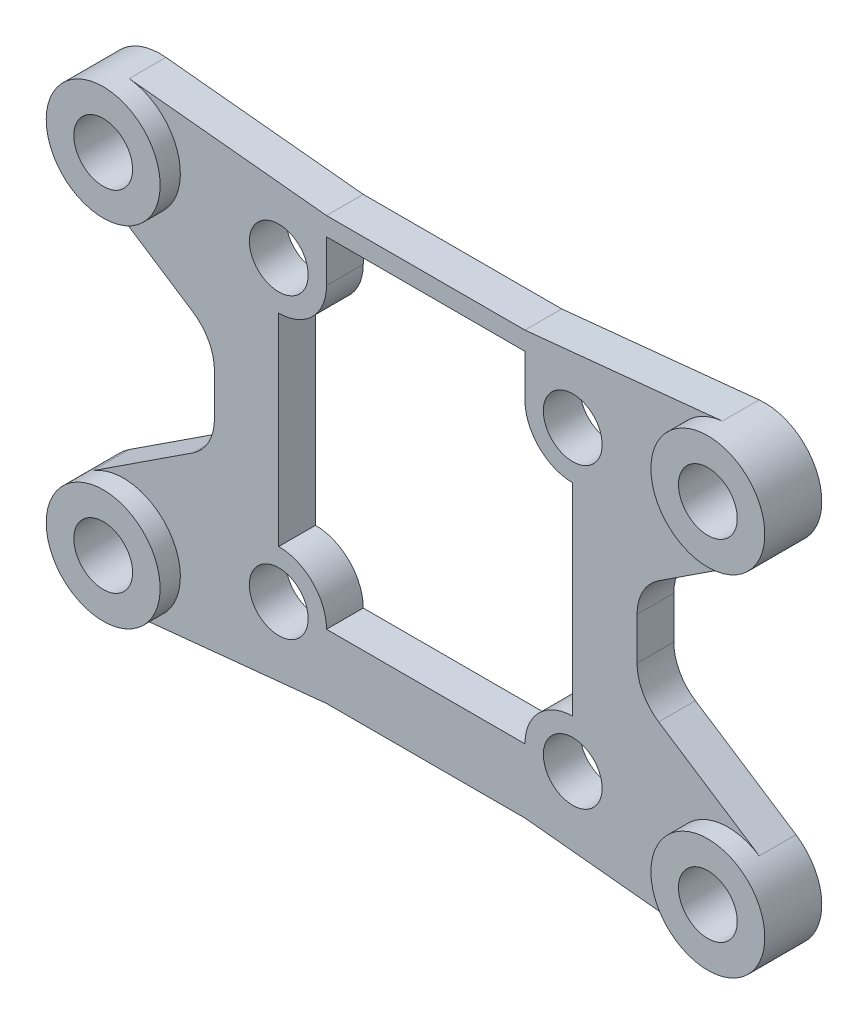
SolidWorks part; units mm, degrees
ref_plane "Front Plane" through (0, 0, 0) normal (0, 0, 1) x (1, 0, 0)
ref_plane "Top Plane" through (0, 0, 0) normal (0, 1, 0) x (1, 0, 0)
ref_plane "Right Plane" through (0, 0, 0) normal (1, 0, 0) x (0, 0, -1)
sketch "Sketch1" plane through (0, 0, 0) normal (0, 0, 1) x (1, 0, 0)
  line L1 (0, 0) -> (23, 0)
  line L2 (0, 0) -> (0, 23)
  line L3 (0, 23) -> (23, 23)
  line L4 (23, 0) -> (23, 23)
  dimension "D1" = 23
  dimension "D2" = 23
extrude "Boss-Extrude1" add sketch "Sketch1" along normal blind 2
fillet "Fillet1" radius 2 4 edges at (23, 23, 1) (23, 0, 1) (0, 0, 1) (0, 23, 1)
sketch "Sketch2" plane through (0, 0, 0) normal (0, 0, 1) x (1, 0, 0)
  line L0 (3.5, 19.7) -> (19.5, 19.7) construction
  line L1 (19.5, 19.7) -> (19.5, 3.5) construction
  line L2 (19.5, 3.5) -> (3.5, 3.5) construction
  line L3 (3.5, 3.5) -> (3.5, 19.7) construction
  line L4 (21, 23) -> (2, 23) construction
  line L5 (23, 2) -> (23, 21) construction
  line L6 (2, 0) -> (21, 0) construction
  line L7 (0, 21) -> (0, 2) construction
  line L8 (3.5, 17.1) -> (3.5, 6.1)
  line L9 (6.1, 3.5) -> (16.9, 3.5)
  line L10 (16.9, 19.7) -> (6.1, 19.7)
  line L11 (19.5, 17.1) -> (19.5, 6.1)
  circle A0 centre (3.5, 19.7) radius 1.6
  circle A1 centre (19.5, 19.7) radius 1.6
  circle A2 centre (19.5, 3.5) radius 1.6
  circle A3 centre (3.5, 3.5) radius 1.6
  arc A4 (6.1, 19.7) -> (3.5, 17.1) centre (3.5, 19.7) cw
  arc A5 (3.5, 6.1) -> (6.1, 3.5) centre (3.5, 3.5) cw
  arc A6 (16.9, 3.5) -> (19.5, 6.1) centre (19.5, 3.5) cw
  arc A7 (16.9, 19.7) -> (19.5, 17.1) centre (19.5, 19.7) ccw
  dimension "D6" = 3.2
  dimension "D7" = 2.6
  dimension "D1" = 3.3
  dimension "D2" = 3.5
  dimension "D3" = 3.5
  dimension "D4" = 3.5
  dimension "D5" = 16
extrude "Cut-Extrude1" cut sketch "Sketch2" along normal blind 2
sketch "Sketch3" plane through (0, 0, 0) normal (0, 0, 1) x (1, 0, 0)
  line L0 (21, 23) -> (2, 23) construction
  line L1 (6.1, 19.7) -> (16.9, 19.7)
  line L2 (6.1, 19.7) -> (6.1, 22)
  line L3 (6.1, 22) -> (16.9, 22)
  line L4 (16.9, 19.7) -> (16.9, 22)
  dimension "D1" = 1
extrude "Cut-Extrude2" cut sketch "Sketch3" along normal blind 2
sketch "Sketch4" plane through (0, 0, 0) normal (0, 0, 1) x (1, 0, 0)
  line L0 (0, 21) -> (0, 2) construction
  line L2 (2, 0) -> (21, 0) construction
  circle A0 centre (11.5, 11.5) radius 14.15 construction
  point P0 (11.5, 11.5)
  point P3 (0, 11.5)
  point P6 (11.5, 0)
  dimension "D1" = 28.3
sketch "Sketch5" plane through (0, 0, 0) normal (0, 0, 1) x (1, 0, 0)
  line L0 (11.5, 11.5) -> (-4.9545, 21) construction
  line L3 (6.1, 23) -> (-6.9654, 24.3187) construction
  line L4 (16.9, 23) -> (21.7765, 21.562)
  line L9 (11.5, 30.5) -> (11.5, -7.5) construction
  line L18 (-7.5, 11.5) -> (30.5, 11.5) construction
  line L40 (21, 23) -> (2, 23) construction
  line L41 (0, 14.0562) -> (-8.8778, 19.8615) construction
  line L42 (0, 21) -> (0, 2) construction
  line L43 (-4.6432, 24.0843) -> (6.1, 23)
  line L44 (6.1, 23) -> (1.2235, 21.562)
  line L45 (1.2235, 21.562) -> (0, 12.6481)
  line L46 (-1.1786, 14.8269) -> (-6.6511, 18.4055)
  line L47 (27.6432, 24.0843) -> (16.9, 23)
  line L48 (24.1786, 14.8269) -> (29.6511, 18.4055)
  line L49 (21.7765, 21.562) -> (23, 12.6481)
  line L50 (16.9, 0) -> (21.7765, 1.438)
  line L51 (27.6432, -1.0843) -> (16.9, 0)
  line L52 (24.1786, 8.1731) -> (29.6511, 4.5945)
  line L53 (21.7765, 1.438) -> (23, 10.3519)
  line L54 (6.1, 0) -> (1.2235, 1.438)
  line L55 (-4.6432, -1.0843) -> (6.1, 0)
  line L56 (-1.1786, 8.1731) -> (-6.6511, 4.5945)
  line L57 (1.2235, 1.438) -> (0, 10.3519)
  circle A0 centre (11.5, 11.5) radius 19 construction
  circle A36 centre (-4.9545, 21) radius 1.6
  circle A37 centre (-4.9545, 21) radius 3.1 construction
  circle A38 centre (-2.6033, 12.6481) radius 2.6033 construction
  circle A39 centre (11.5, 11.5) radius 14.15 construction
  arc A40 (0, 12.6481) -> (-1.1786, 14.8269) centre (-2.6033, 12.6481) ccw
  arc A41 (-4.6432, 24.0843) -> (-6.6511, 18.4055) centre (-4.9545, 21) ccw
  circle A42 centre (27.9545, 21) radius 1.6
  arc A43 (27.6432, 24.0843) -> (29.6511, 18.4055) centre (27.9545, 21) cw
  arc A44 (23, 12.6481) -> (24.1786, 14.8269) centre (25.6033, 12.6481) cw
  circle A45 centre (27.9545, 2) radius 1.6
  arc A46 (27.6432, -1.0843) -> (29.6511, 4.5945) centre (27.9545, 2) ccw
  arc A47 (23, 10.3519) -> (24.1786, 8.1731) centre (25.6033, 10.3519) ccw
  circle A48 centre (-4.9545, 2) radius 1.6
  arc A49 (-4.6432, -1.0843) -> (-6.6511, 4.5945) centre (-4.9545, 2) cw
  arc A50 (0, 10.3519) -> (-1.1786, 8.1731) centre (-2.6033, 10.3519) cw
  point P62 (11.5, 11.5)
  dimension "D1" = 38
  dimension "D2" = 3.2
  dimension "D3" = 6.2
  dimension "D4" = 60
extrude "Boss-Extrude2" add sketch "Sketch5" along normal blind 2 from surface separate body starting at face at (21.1, 19.7, 0)
combine bodies "Combine1" operation type add bodies to combine 118 103 115 116 117
sketch "Sketch6" plane through (0, 0, 0) normal (0, 0, 1) x (1, 0, 0)
  circle A0 centre (-4.9545, 21) radius 3.1
  circle A1 centre (-4.9545, 2) radius 3.1
  circle A2 centre (27.9545, 2) radius 3.1
  circle A3 centre (27.9545, 21) radius 3.1
  circle A4 centre (-4.9545, 21) radius 1.6
  circle A5 centre (-4.9545, 2) radius 1.6
  circle A6 centre (27.9545, 2) radius 1.6
  circle A7 centre (27.9545, 21) radius 1.6
extrude "Boss-Extrude3" add sketch "Sketch6" along normal blind 1.1 from surface starting at face at (11.5, 11.5, 2)
